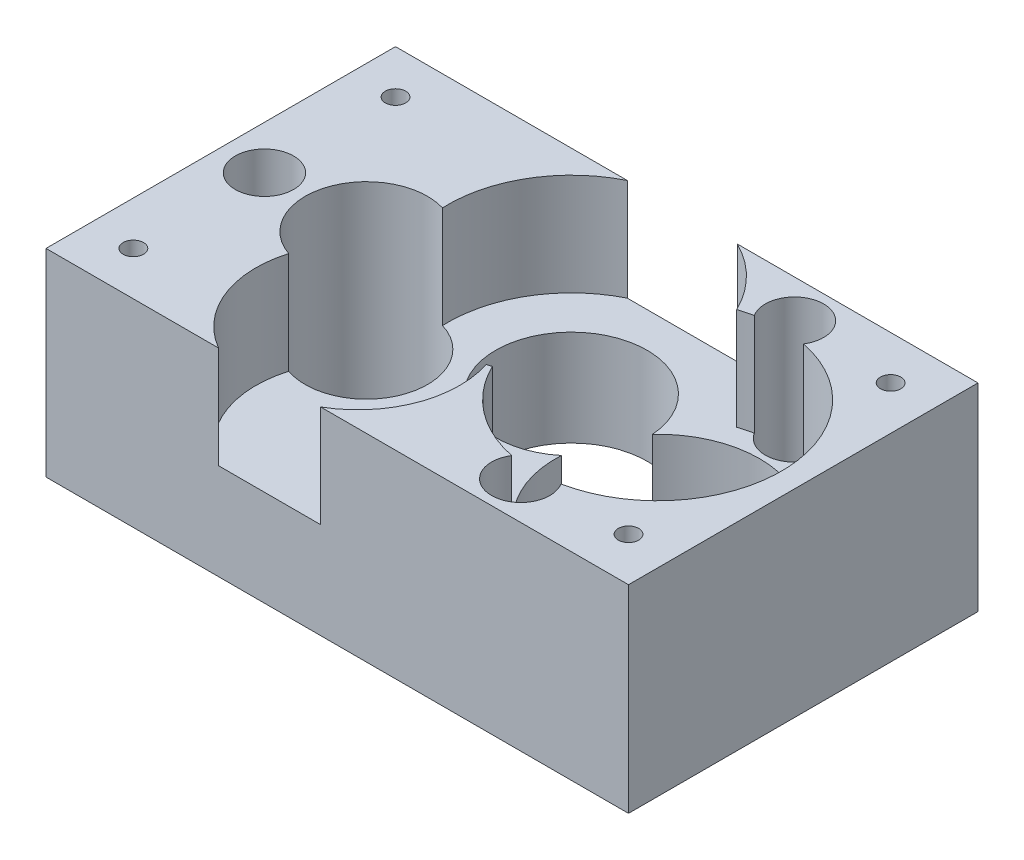
SolidWorks part; units mm, degrees
note: The reader was unsure of these and kept them because the rebuilt part matched: shared geometry of "草图1<6>", "草图2<4>".
ref_plane "前视基准面" through (0, 0, 0) normal (0, 0, 1) x (1, 0, 0)
ref_plane "上视基准面" through (0, 0, 0) normal (0, 1, 0) x (1, 0, 0)
ref_plane "右视基准面" through (0, 0, 0) normal (1, 0, 0) x (0, 0, -1)
other "Configuration Table"
sketch "草图1" plane through (0, 0, 0) normal (0, 1, 0) x (1, 0, 0)
  line L1 (0, 0) -> (20, 0)
  line L2 (0, 0) -> (0, -12)
  line L3 (0, -12) -> (20, -12)
  line L4 (20, 0) -> (20, -12)
  circle A0 centre (5, -6) radius 2.1
  circle A4 centre (15, -6) radius 3.5
  circle A6 centre (7.6787, -8.9706) radius 0.6
  circle A7 centre (7.6787, -8.9706) radius 3.5
  circle A8 centre (9.8471, -3.8074) radius 2.6
  circle A9 centre (9.8471, -3.8074) radius 4.25
  circle A10 centre (15, -6) radius 4.25
  dimension "D2" = 4.2
  dimension "D3" = 5.6
  dimension "D6" = 8.5
  dimension "D4" = 20
  dimension "D5" = 7
  dimension "D7" = 7
  dimension "D14" = 1.2
  dimension "D15" = 5.2
  dimension "D17" = 8.5
  dimension "D8" = 4
  dimension "D9" = 5
  dimension "D10" = 6
  dimension "D11" = 12
  dimension "D12" = 5.6
  dimension "D13" = 10
  dimension "D16" = 3.0294
extrude "凸台-拉伸1" add sketch "草图1" along normal blind 3.3
extrude "凸台-拉伸4" add sketch "草图1<6>" along normal blind 3.5 from surface contours A9 L1 L2 L3 A7 A0 | A9 A7 L3 L4 L1 A4
sketch "草图1<6>" plane through (0, 0, 0) normal (0, 1, 0) x (1, 0, 0) same geometry as "草图1"
sketch "草图2" plane through (5, -17.2, 6) normal (0, 1, 0) x (0, 0, -1)
  circle A0 centre (0, 3.5) radius 1
  circle A1 centre (0, 3.5) radius 0.75
  circle A2 centre (-4.7, -10) radius 1
  circle A3 centre (-4.7, -10) radius 0.75
  circle A4 centre (4.7, -10) radius 1
  circle A5 centre (4.7, -10) radius 0.75
  dimension "D1" = 1.5
  dimension "D2" = 2
extrude "切除-拉伸1" cut sketch "草图2" along normal through all contours A1 | A3 | A5
extrude "切除-拉伸2" cut sketch "草图2<4>" against normal offset from surface (5.8 mm away) 1 from surface at 24 contours A2 | A4 | A0 up to face at (1.5, 0, 6.75) starting at face at (1.5, 6.8, 6.75)
sketch "草图2<4>" plane through (5, -17.2, 6) normal (0, 1, 0) x (0, 0, -1) same geometry as "草图2"
sketch "草图3" plane through (0, 0, 0) normal (0, 1, 0) x (1, 0, 0)
  circle A0 centre (1.5, -1.5) radius 0.35
  circle A1 centre (1.5, -10.5) radius 0.35
  circle A2 centre (18.5, -10.5) radius 0.35
  circle A3 centre (18.5, -1.5) radius 0.35
  dimension "D1" = 0.7
  dimension "D2" = 1.5
  dimension "D3" = 1.5
  dimension "D4" = 18.5
  dimension "D5" = 10.5
extrude "切除-拉伸3" cut sketch "草图3" along normal through all
